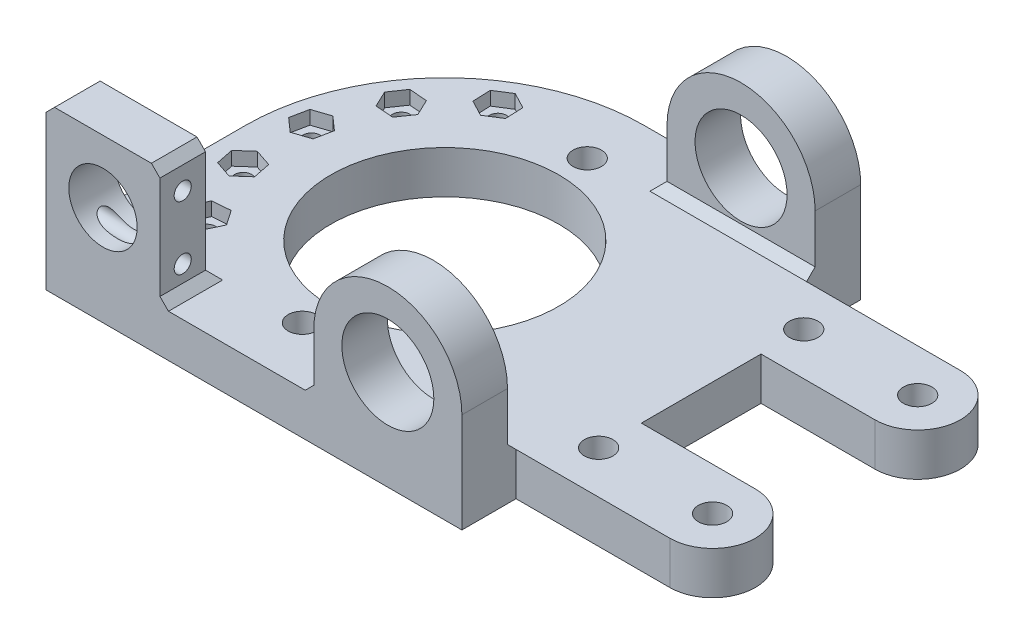
SolidWorks part; units mm, degrees
ref_plane "Front Plane" through (0, 0, 0) normal (0, 0, 1) x (1, 0, 0)
ref_plane "Top Plane" through (0, 0, 0) normal (0, 1, 0) x (1, 0, 0)
ref_plane "Right Plane" through (0, 0, 0) normal (1, 0, 0) x (0, 0, -1)
sketch "Sketch1" plane through (0, 0, 0) normal (0, 1, 0) x (1, 0, 0)
  line L0 (-62.4163, 0) -> (61.9965, 0) construction
  line L1 (-36.5, 35) -> (36.5, 35)
  line L2 (-36.5, 35) -> (-36.5, -35)
  line L3 (-36.5, -35) -> (36.5, -35)
  line L4 (36.5, 35) -> (36.5, -35) construction
  line L5 (-36.5, 35) -> (36.5, -35) construction
  line L6 (-36.5, -35) -> (36.5, 35) construction
  line L7 (36.5, 35) -> (36.5, 25.5)
  line L8 (36.5, 25.5) -> (63.5, 25.5)
  line L9 (63.5, 10.5) -> (43.5, 10.5)
  line L10 (43.5, 10.5) -> (43.5, -10.5)
  line L11 (63.5, -10.5) -> (43.5, -10.5)
  line L12 (36.5, -25.5) -> (63.5, -25.5)
  line L13 (36.5, -35) -> (36.5, -25.5)
  arc A0 (63.5, 25.5) -> (63.5, 10.5) centre (63.5, 18) cw
  arc A1 (63.5, -25.5) -> (63.5, -10.5) centre (63.5, -18) ccw
  point P0 (0, 0)
  point P15 (43.5, 0)
  dimension "D1" = 73
  dimension "D2" = 70
  dimension "D3" = 80
  dimension "D4" = 15
  dimension "D5" = 20
  dimension "D6" = 9.5
extrude "Boss-Extrude1" add sketch "Sketch1" along normal blind 7.5
sketch "Sketch3" plane through (0, 0, 35) normal (0, 0, 1) x (1, 0, 0)
  line L0 (36.5, 7.5) -> (36.5, 0) construction
  line L1 (36.5, 7.5) -> (10.5, 7.5)
  line L2 (36.5, 7.5) -> (36.5, 17.5)
  line L3 (36.5, 17.5) -> (10.5, 17.5) construction
  line L4 (10.5, 7.5) -> (10.5, 17.5)
  line L5 (-36.5, 7.5) -> (36.5, 7.5) construction
  line L6 (-36.5, 0) -> (36.5, 0) construction
  circle A0 centre (23.5, 17.5) radius 8.075
  arc A1 (10.5, 17.5) -> (36.5, 17.5) centre (23.5, 17.5) cw
  point P10 (23.5, 17.5)
  dimension "D3" = 16.15
  dimension "D1" = 26
  dimension "D2" = 17.5
extrude "Boss-Extrude3" add sketch "Sketch3" against normal blind 8
mirror "Mirror1" about plane through (0, 0, 0) normal (0, 0, 1) of "Boss-Extrude3"
sketch "Sketch10" plane through (0, 0, 0) normal (0, -1, 0) x (1, 0, 0)
  line L1 (-36.5, 27) -> (-16.5, 27)
  line L2 (-36.5, 27) -> (-36.5, 35)
  line L3 (-36.5, 35) -> (-16.5, 35)
  line L4 (-16.5, 27) -> (-16.5, 35)
  line L6 (-36.5, 35) -> (36.5, 35) construction
  line L7 (31.575, 35) -> (15.425, 35) construction
  point P9 (23.5, 35)
  point P14 (-26.5, 35)
  dimension "D1" = 8
  dimension "D4" = 50
extrude "Boss-Extrude4" add sketch "Sketch10" against normal offset from surface (28.5 mm away) 21 up to face at (27.1563, 7.5, -0.2031) offset beyond the face yes
sketch "Sketch11" plane through (0, 0, 35) normal (0, 0, 1) x (1, 0, 0)
  circle A0 centre (-26.5, 17.5) radius 6
  point P2 (23.5, 17.5)
  dimension "D1" = 12
  dimension "D2" = 50
extrude "Cut-Extrude6" cut sketch "Sketch11" against normal up to next
sketch "Sketch12" plane through (-36.5, 0, 0) normal (-1, 0, 0) x (0, 0, 1)
  line L0 (27, 17.5) -> (35, 17.5) construction
  line L1 (27, 28.5) -> (27, 7.5) construction
  line L2 (35, 28.5) -> (35, 0) construction
  line L3 (27, 23.5) -> (27, 11.5) construction
  circle A0 centre (31, 23.05) radius 1.5
  circle A1 centre (31, 11.95) radius 1.5
  point P12 (31, 21.55)
  point P13 (31, 13.45)
  point P14 (31, 17.5)
  dimension "D2" = 3
  dimension "D1" = 8.1
extrude "Cut-Extrude7" cut sketch "Sketch12" against normal up to next
sketch "Sketch6" plane through (0, 0, 0) normal (0, -1, 0) x (1, 0, 0)
  line L0 (-36.5, -35) -> (-36.5, 35) construction
  line L3 (-36.5, 35) -> (36.5, 35) construction
  line L5 (-20.5, 35) -> (-32.5, 35) construction
  line L6 (31.575, 35) -> (15.425, 35) construction
  line L7 (-26.5, 35) -> (23.5, 35) construction
  line L9 (-1.5, 35) -> (-1.5, 0) construction
  circle A0 centre (-1.5, 0) radius 20
  point P3 (-26.5, 35)
  point P5 (-36.5, 0)
  point P10 (23.5, 35)
  point P18 (-1.5, 35)
  dimension "D1" = 40
extrude "Cut-Extrude3" cut sketch "Sketch6" against normal through all
sketch "Sketch15" plane through (0, 0, 0) normal (0, -1, 0) x (1, 0, 0)
  line L0 (-1.5, 35) -> (-1.5, -35) construction
  line L1 (-36.5, 35) -> (36.5, 35) construction
  line L2 (36.5, -35) -> (-36.5, -35) construction
  line L3 (-21.5, 0) -> (18.5, 0) construction
  circle A1 centre (-1.5, 0) radius 20 construction
  circle A2 centre (-1.5, 25) radius 2.5
  circle A3 centre (-1.5, -25) radius 2.5
  point P8 (-1.5, 0)
  dimension "D1" = 5
  dimension "D2" = 25
extrude "Cut-Extrude9" cut sketch "Sketch15" against normal through all
sketch "Sketch14" plane through (0, 0, 0) normal (0, -1, 0) x (1, 0, 0)
  line L0 (0, 0) -> (89.7656, 0) construction
  line L1 (53.5, -10.5) -> (53.5, -25.5333) construction
  circle A0 centre (63.5, -18) radius 2.5
  circle A1 centre (43.5, -18) radius 2.5
  circle A2 centre (63.5, 18) radius 2.5
  circle A3 centre (43.5, 18) radius 2.5
  dimension "D1" = 5
  dimension "D2" = 20
extrude "Cut-Extrude8" cut sketch "Sketch14" against normal through all
fillet "Fillet2" radius 35 1 edges at (-36.5, 3.75, -35)
chamfer "Chamfer2" distance 1.5 angle 45 8 edges at (-16.5, 28.5, 31) (-36.5, 28.5, 31) (-26.5, 7.5, 27) (-16.5, 7.5, 31) (23.5, 7.5, -27) (10.5, 7.5, -31)
sketch "Sketch17" plane through (0, 0, 0) normal (0, -1, 0) x (1, 0, 0)
  line L0 (-1.5, 0) -> (-36.5, 0) construction
  line L1 (-1.5, 0) -> (-16.5, -25.9808) construction
  line L2 (-1.5, 0) -> (-27.4808, 15) construction
  line L3 (-26.1909, 17.04) -> (-30.8939, 6) construction
  line L4 (-30.8939, 6) -> (-30.8939, -6) construction
  line L5 (-30.8939, -6) -> (-26.1909, -17.04) construction
  line L6 (-26.1909, -17.04) -> (-17.5373, -25.3536) construction
  circle A0 centre (-1.5, 0) radius 30 construction
  circle A1 centre (-30.8939, 6) radius 1.5
  circle A2 centre (-30.8939, -6) radius 1.5
  circle A3 centre (-26.1909, 17.04) radius 1.5
  circle A4 centre (-26.1909, -17.04) radius 1.5
  circle A5 centre (-17.5373, -25.3536) radius 1.5
  point P0 (-1.5, 0)
  point P5 (-31.5, 0)
  dimension "D2" = 60
  dimension "D5" = 3
  dimension "D1" = 30
  dimension "D3" = 5
  dimension "D4" = 12
extrude "Cut-Extrude11" cut sketch "Sketch17" against normal up to next
sketch "Sketch18" plane through (0, 7.5, 0) normal (0, 1, 0) x (1, 0, 0)
  line L0 (-26.1909, -17.04) -> (-1.5, 0) construction
  line L1 (-23.0257, -16.7847) -> (-24.8293, -14.1713)
  line L2 (-24.8293, -14.1713) -> (-27.9945, -14.4265)
  line L3 (-27.9945, -14.4265) -> (-29.356, -17.2953)
  line L4 (-29.356, -17.2953) -> (-27.5524, -19.9087)
  line L5 (-27.5524, -19.9087) -> (-24.3872, -19.6535)
  line L6 (-24.3872, -19.6535) -> (-23.0257, -16.7847)
  line L7 (-28.517, -3.8944) -> (-31.529, -2.8887)
  line L8 (-31.529, -2.8887) -> (-33.9059, -4.9944)
  line L9 (-33.9059, -4.9944) -> (-33.2708, -8.1056)
  line L10 (-33.2708, -8.1056) -> (-30.2588, -9.1113)
  line L11 (-30.2588, -9.1113) -> (-27.8819, -7.0056)
  line L12 (-27.8819, -7.0056) -> (-28.517, -3.8944)
  line L13 (-27.8819, 7.0056) -> (-30.2588, 9.1113)
  line L14 (-30.2588, 9.1113) -> (-33.2708, 8.1056)
  line L15 (-33.2708, 8.1056) -> (-33.9059, 4.9944)
  line L16 (-33.9059, 4.9944) -> (-31.529, 2.8887)
  line L17 (-31.529, 2.8887) -> (-28.517, 3.8944)
  line L18 (-28.517, 3.8944) -> (-27.8819, 7.0056)
  line L19 (-23.0257, 16.7847) -> (-24.3872, 19.6535)
  line L20 (-24.3872, 19.6535) -> (-27.5524, 19.9087)
  line L21 (-27.5524, 19.9087) -> (-29.356, 17.2953)
  line L22 (-29.356, 17.2953) -> (-27.9945, 14.4265)
  line L23 (-27.9945, 14.4265) -> (-24.8293, 14.1713)
  line L24 (-24.8293, 14.1713) -> (-23.0257, 16.7847)
  line L25 (-14.7254, 23.8783) -> (-14.8537, 27.0511)
  line L26 (-14.8537, 27.0511) -> (-17.6656, 28.5264)
  line L27 (-17.6656, 28.5264) -> (-20.3492, 26.8289)
  line L28 (-20.3492, 26.8289) -> (-20.2209, 23.6561)
  line L29 (-20.2209, 23.6561) -> (-17.409, 22.1808)
  line L30 (-17.409, 22.1808) -> (-14.7254, 23.8783)
  line L31 (-1.5, 0) -> (-30.8939, -6) construction
  line L32 (-1.5, 0) -> (-30.8939, 6) construction
  line L33 (-1.5, 0) -> (-26.1909, 17.04) construction
  line L34 (-1.5, 0) -> (-17.5373, 25.3536) construction
  circle A0 centre (-26.1909, -17.04) radius 2.75 construction
  circle A1 centre (-30.8939, -6) radius 2.75 construction
  circle A2 centre (-30.8939, 6) radius 2.75 construction
  circle A3 centre (-26.1909, 17.04) radius 2.75 construction
  circle A4 centre (-17.5373, 25.3536) radius 2.75 construction
  point P0 (-26.1909, -17.04)
  point P1 (-30.8939, -6)
  point P3 (-30.8939, 6)
  point P5 (-26.1909, 17.04)
  point P7 (-17.5373, 25.3536)
  point P43 (-1.5, 0)
  dimension "D1" = 5.5
extrude "Cut-Extrude12" cut sketch "Sketch18" against normal blind 2.4
